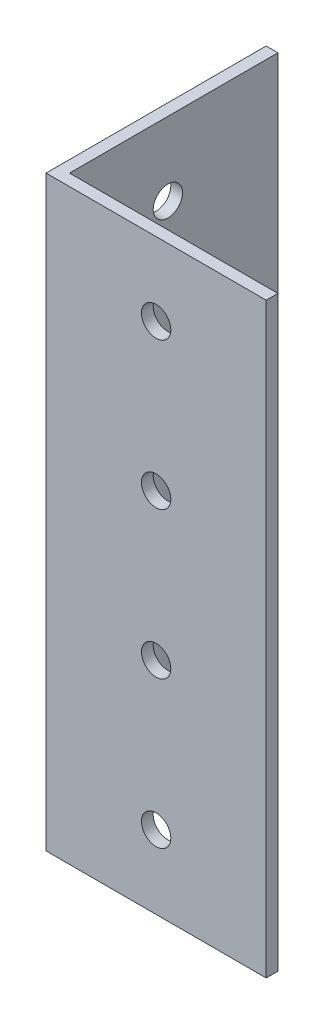
SolidWorks part; units mm, degrees
ref_plane "Спереди" through (0, 0, 0) normal (0, 0, 1) x (1, 0, 0)
ref_plane "Сверху" through (0, 0, 0) normal (0, 1, 0) x (1, 0, 0)
ref_plane "Справа" through (0, 0, 0) normal (1, 0, 0) x (0, 0, -1)
sketch "Эскиз1" plane through (0, 0, 0) normal (0, 1, 0) x (1, 0, 0)
  line L0 (0, 0) -> (75, 0)
  line L1 (0, 0) -> (0, 75)
extrude "Вытянуть-Тонкостенный1" add sketch "Эскиз1" along normal blind 200 thin thin type one direction wall 4
sketch "Эскиз2" plane through (0, 0, 0) normal (0, 0, 1) x (1, 0, 0)
  circle A0 centre (37.5, 175) radius 5
  circle A1 centre (37.5, 125) radius 5
  circle A2 centre (37.5, 75) radius 5
  circle A3 centre (37.5, 25) radius 5
  dimension "D1" = 4
extrude "Вырез-Вытянуть1" cut sketch "Эскиз2" against normal blind 10
sketch "Эскиз3" plane through (0, 0, 0) normal (-1, 0, 0) x (0, 0, 1)
  circle A0 centre (-37.5, 175) radius 5
  circle A1 centre (-37.5, 125) radius 5
  circle A2 centre (-37.5, 75) radius 5
  circle A3 centre (-37.5, 25) radius 5
  dimension "D1" = 4
extrude "Вырез-Вытянуть2" cut sketch "Эскиз3" against normal blind 10
